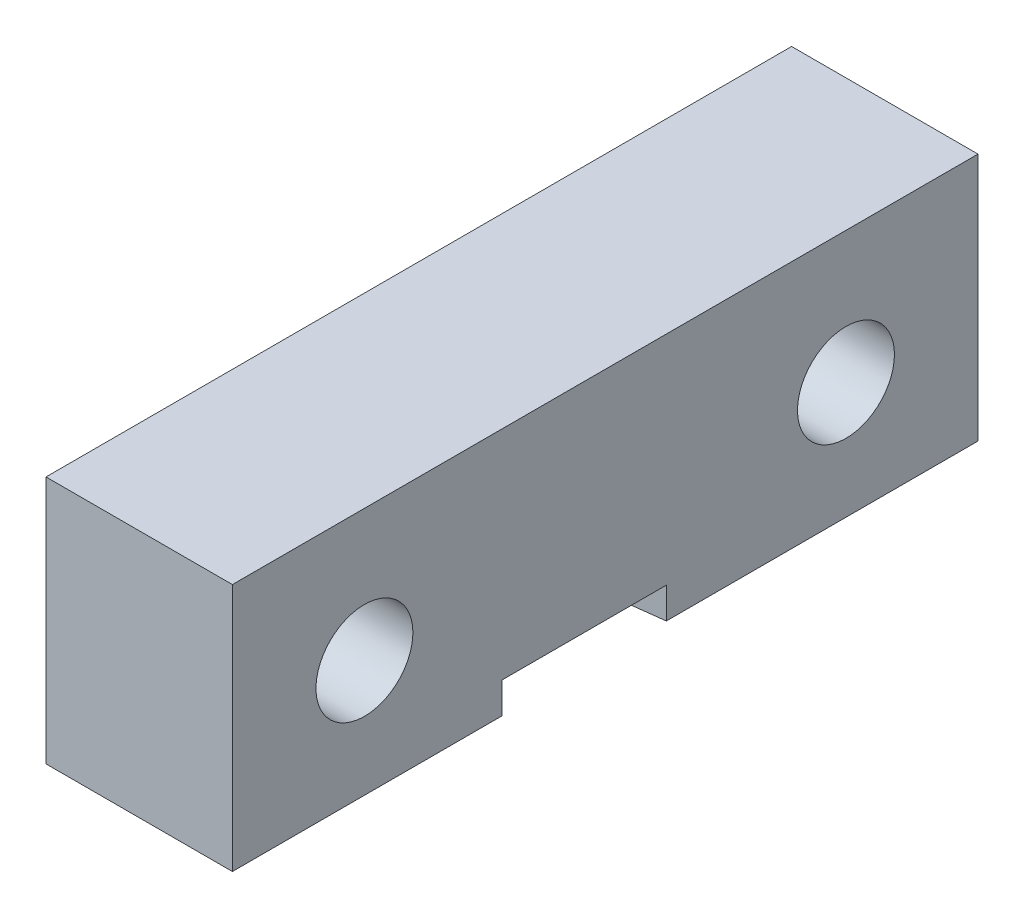
SolidWorks part; units mm, degrees
ref_plane "Front Plane" through (0, 0, 0) normal (0, 0, 1) x (1, 0, 0)
ref_plane "Top Plane" through (0, 0, 0) normal (0, 1, 0) x (1, 0, 0)
ref_plane "Right Plane" through (0, 0, 0) normal (1, 0, 0) x (0, 0, -1)
sketch "Sketch1" plane through (0, 0, 0) normal (0, 0, 1) x (1, 0, 0)
  line L1 (19.05, -25.4) -> (-19.05, -25.4)
  line L2 (19.05, -25.4) -> (19.05, 25.4)
  line L3 (19.05, 25.4) -> (-19.05, 25.4)
  line L4 (-19.05, -25.4) -> (-19.05, 25.4)
  line L5 (19.05, -25.4) -> (-19.05, 25.4) construction
  line L6 (19.05, 25.4) -> (-19.05, -25.4) construction
  point P0 (0, 0)
  dimension "D1" = 38.1
  dimension "D2" = 50.8
extrude "Boss-Extrude1" add sketch "Sketch1" along normal mid plane 152.4
sketch "Sketch2" plane through (19.05, 0, 0) normal (1, 0, 0) x (0, 0, -1)
  line L0 (-76.2, -25.4) -> (76.2, -25.4) construction
  circle A0 centre (-49.2125, -1.524) radius 6.731
  circle A1 centre (49.2125, -1.524) radius 6.731
  dimension "D4" = 13.462
  dimension "D1" = 98.425
  dimension "D2" = 49.2125
  dimension "D3" = 23.876
extrude "Cut-Extrude1" cut sketch "Sketch2" against normal up to next
sketch "Sketch3" plane through (19.05, 0, 0) normal (1, 0, 0) x (0, 0, -1)
  circle A0 centre (-49.2125, -1.524) radius 9.906
  circle A1 centre (49.2125, -1.524) radius 9.906
  dimension "D1" = 19.812
extrude "Cut-Extrude2" cut sketch "Sketch3" against normal blind 38.608
sketch "Sketch4" plane through (0, -25.4, 0) normal (0, -1, 0) x (1, 0, 0)
  line L4 (19.05, -12.4961) -> (19.05, 21.1376)
  line L5 (19.05, 76.2) -> (19.05, -76.2) construction
  line L6 (19.05, -12.4961) -> (0.9472, -10.2486)
  line L7 (19.05, 21.1376) -> (0.9472, 18.8901)
  circle A1 centre (2.756, 4.3208) radius 14.6812 construction
  arc A4 (0.9472, 18.8901) -> (0.9472, -10.2486) centre (2.756, 4.3208) ccw
extrude "Cut-Extrude3" cut sketch "Sketch4" against normal blind 6.35
sketch "Sketch5" plane through (0, -19.05, 0) normal (0, -1, 0) x (1, 0, 0)
  circle A0 centre (2.756, 4.3208) radius 12.0142
extrude "Cut-Extrude4" cut sketch "Sketch5" against normal blind 3.81
sketch "Sketch6" plane through (0, -19.05, 0) normal (0, -1, 0) x (1, 0, 0)
  circle A0 centre (2.756, 4.3208) radius 14.6812
extrude "Cut-Extrude5" cut sketch "Sketch6" against normal blind 1.5875
